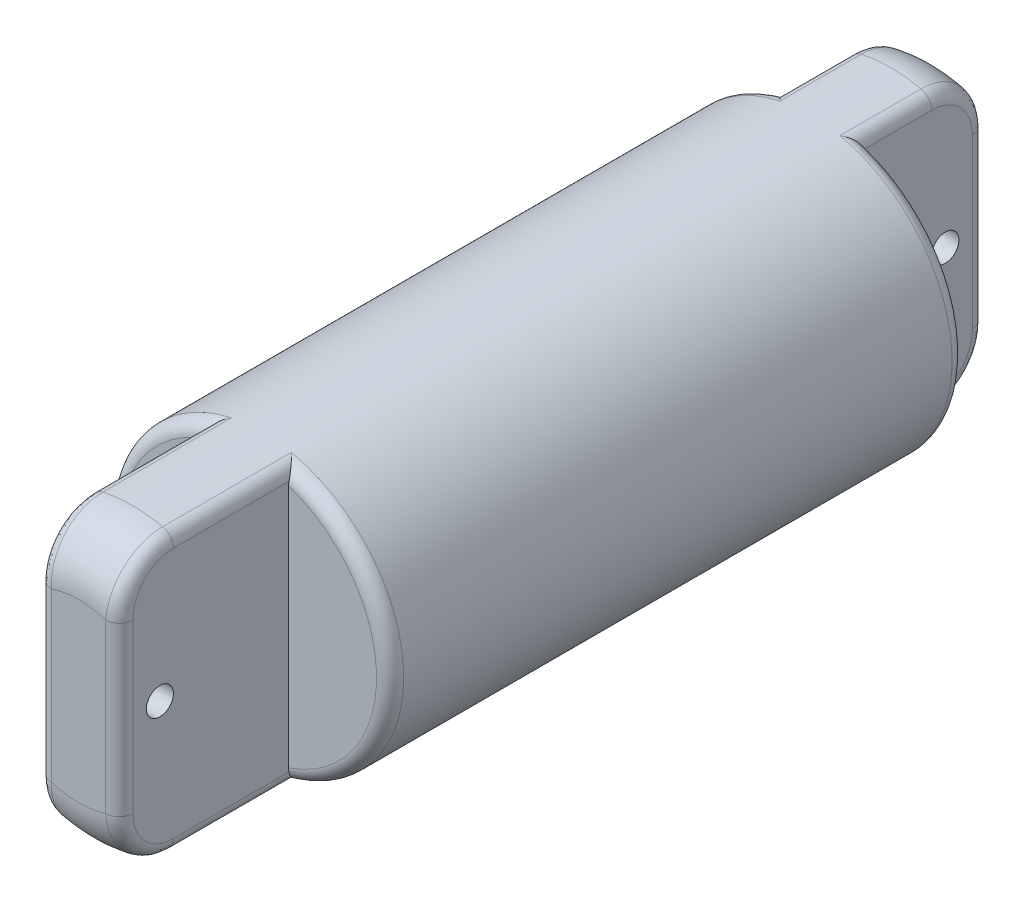
SolidWorks part; units mm, degrees
ref_plane "Alzado" through (0, 0, 0) normal (0, 0, 1) x (1, 0, 0)
ref_plane "Planta" through (0, 0, 0) normal (0, 1, 0) x (1, 0, 0)
ref_plane "Vista lateral" through (0, 0, 0) normal (1, 0, 0) x (0, 0, -1)
sketch "Croquis1" plane through (0, 0, 0) normal (0, 0, 1) x (1, 0, 0)
  circle A0 centre (0, 0) radius 10.5
  dimension "D1" = 21
extrude "Saliente-Extruir1" add sketch "Croquis1" along normal blind 64
sketch "Croquis2" plane through (0, 0, 0) normal (0, 0, -1) x (-1, 0, 0)
  line L0 (0, 10.5) -> (0, -10.5) construction
  line L1 (0, 0) -> (3, 0) construction
  line L2 (-13, -11) -> (-3, -11)
  line L3 (-13, -11) -> (-13, 11)
  line L4 (-13, 11) -> (-3, 11)
  line L5 (-3, -11) -> (-3, 11)
  line L6 (-13, -11) -> (-3, 11) construction
  line L7 (-13, 11) -> (-3, -11) construction
  line L8 (13, -11) -> (3, -11)
  line L9 (13, -11) -> (13, 11)
  line L10 (13, 11) -> (3, 11)
  line L11 (3, -11) -> (3, 11)
  line L12 (13, -11) -> (3, 11) construction
  line L13 (13, 11) -> (3, -11) construction
  line L14 (0, 0) -> (-3, 0) construction
  circle A0 centre (0, 0) radius 10.5 construction
  point P5 (-8, 0)
  point P10 (8, 0)
  dimension "D1" = 3
  dimension "D2" = 3
  dimension "D3" = 22
  dimension "D4" = 10
  dimension "D5" = 22
  dimension "D6" = 10
extrude "Cortar-Extruir1" cut sketch "Croquis2" against normal blind 9
sketch "Croquis3" plane through (3, 0, 0) normal (1, 0, 0) x (0, 0, -1)
  line L0 (0, 0) -> (-3, 0) construction
  circle A0 centre (-3, 0) radius 1
  dimension "D2" = 2
  dimension "D1" = 3
extrude "Cortar-Extruir2" cut sketch "Croquis3" against normal blind 6
sketch "Croquis5" plane through (0, 0, 0) normal (1, 0, 0) x (0, 0, -1)
  line L0 (-64, 0) -> (-61, 0) construction
  line L1 (-64, 10.5) -> (-64, -10.5) construction
  circle A0 centre (-61, 0) radius 1
  dimension "D2" = 2
  dimension "D1" = 3
extrude "Cortar-Extruir4" cut sketch "Croquis5" against normal mid plane 12
sketch "Croquis6" plane through (0, 0, 64) normal (0, 0, 1) x (1, 0, 0)
  line L0 (0, 10.5) -> (0, -10.5) construction
  line L1 (0, 0) -> (-3, 0) construction
  line L2 (-13, -11) -> (-3, -11)
  line L3 (-13, -11) -> (-13, 11)
  line L4 (-13, 11) -> (-3, 11)
  line L5 (-3, -11) -> (-3, 11)
  line L6 (-13, -11) -> (-3, 11) construction
  line L7 (-13, 11) -> (-3, -11) construction
  line L8 (13, -11) -> (3, -11)
  line L9 (13, -11) -> (13, 11)
  line L10 (13, 11) -> (3, 11)
  line L11 (3, -11) -> (3, 11)
  line L12 (13, -11) -> (3, 11) construction
  line L13 (13, 11) -> (3, -11) construction
  line L14 (0, 0) -> (3, 0) construction
  circle A0 centre (0, 0) radius 10.5 construction
  point P5 (-8, 0)
  point P10 (8, 0)
  dimension "D1" = 3
  dimension "D2" = 3
  dimension "D3" = 22
  dimension "D4" = 10
  dimension "D5" = 22
  dimension "D6" = 10
extrude "Cortar-Extruir5" cut sketch "Croquis6" against normal blind 12.5
fillet "Redondeo2" radius 4 2 edges at (0, 10.5, 64) (0, -10.5, 64)
fillet "Redondeo3" radius 4 2 edges at (0, 10.5, 0) (0, -10.5, 0)
fillet "Redondeo4" radius 1 4 edges at (-10.5, 0, 51.5) (-10.5, 0, 9) (10.5, 0, 51.5) (10.5, 0, 9)
fillet "Redondeo5" radius 1 20 edges at (-3, -10.0623, 55.25) (-3, -9.2149, 62.412) (-3, 0, 64) (-3, 10.0623, 55.25) (3, 10.0623, 55.25) (3, 9.2149, 62.412) (3, -10.0623, 55.25) (3, -8.7509, 62.9039) (3, 10.0623, 7) (3, 8.7509, 1.0961) (3, -10.0623, 7) (3, -9.2149, 1.588) (-3, 10.0623, 7) (-3, -10.0623, 7) (-3, -8.7509, 1.0961) (-3, 0, 0) (-3, 8.7509, 62.9039) (3, 0, 64) (3, 0, 0) (-3, 9.2149, 1.588)
